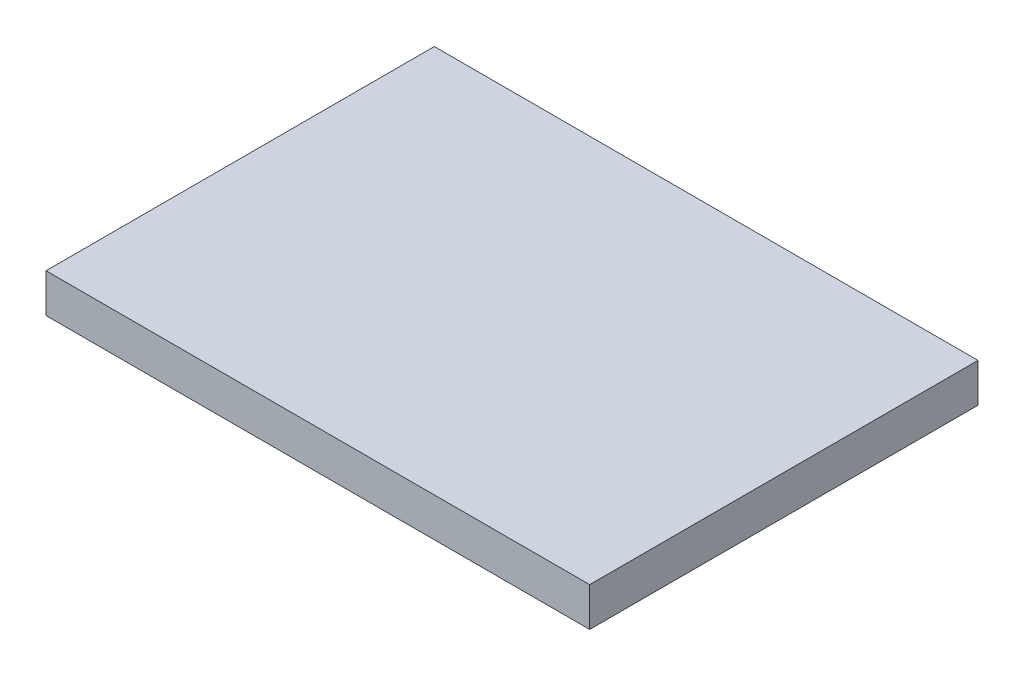
SolidWorks part; units mm, degrees
material "Mahogany"
ref_plane "Front Plane" through (0, 0, 0) normal (0, 0, 1) x (1, 0, 0)
ref_plane "Top Plane" through (0, 0, 0) normal (0, 1, 0) x (1, 0, 0)
ref_plane "Right Plane" through (0, 0, 0) normal (1, 0, 0) x (0, 0, -1)
sketch "Sketch1" plane through (0, 0, 0) normal (0, 1, 0) x (1, 0, 0)
  line L1 (-88.9, 63.5) -> (88.9, 63.5)
  line L2 (-88.9, 63.5) -> (-88.9, -63.5)
  line L3 (-88.9, -63.5) -> (88.9, -63.5)
  line L4 (88.9, 63.5) -> (88.9, -63.5)
  line L5 (-88.9, 63.5) -> (88.9, -63.5) construction
  line L6 (-88.9, -63.5) -> (88.9, 63.5) construction
  point P0 (0, 0)
  dimension "D1" = 177.8
  dimension "D2" = 127
extrude "Boss-Extrude1" add sketch "Sketch1" along normal blind 12.7
ref_axis "Axis1" through (0, 0, 0) along (0, 1, 0)
